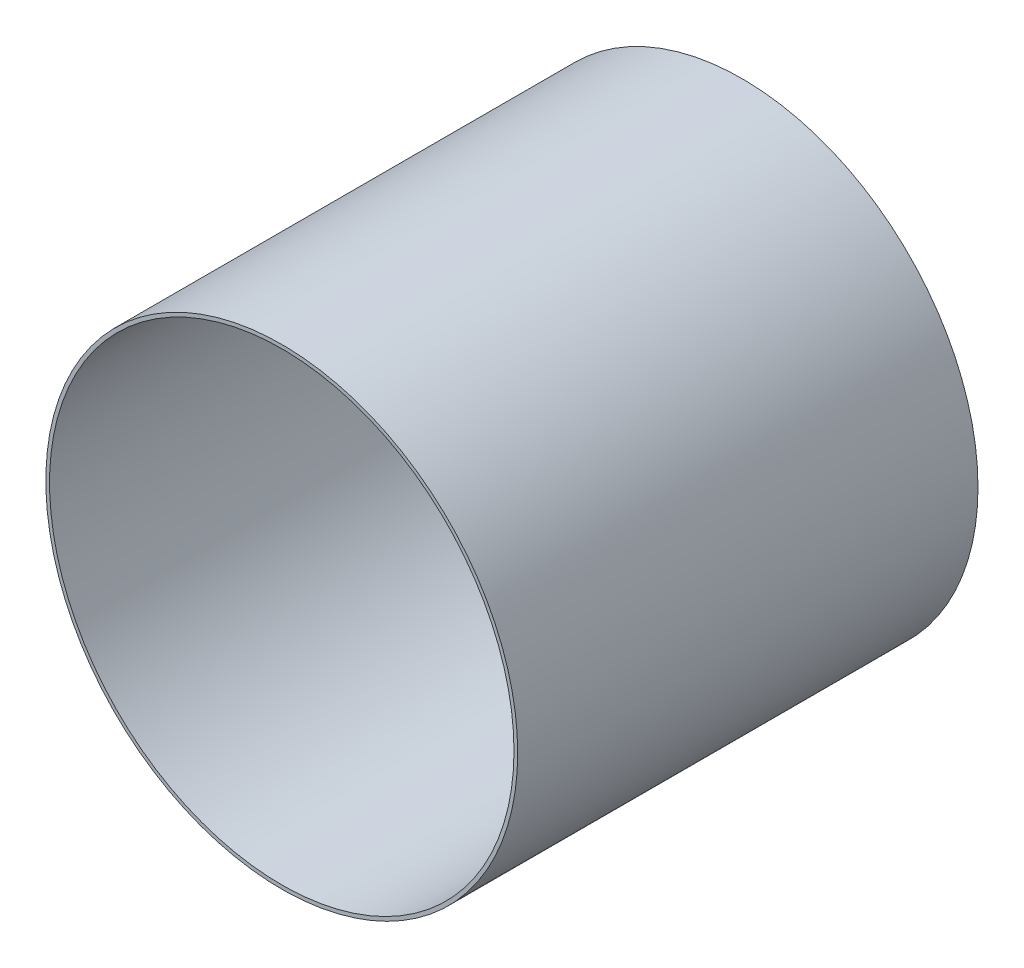
SolidWorks part; units mm, degrees
material "Titanio"
ref_plane "Piano frontale" through (0, 0, 0) normal (0, 0, 1) x (1, 0, 0)
ref_plane "Piano superiore" through (0, 0, 0) normal (0, 1, 0) x (1, 0, 0)
ref_plane "Piano destro" through (0, 0, 0) normal (1, 0, 0) x (0, 0, -1)
sketch "Schizzo1" plane through (0, 0, 0) normal (0, 0, 1) x (1, 0, 0)
  circle A0 centre (0, 0) radius 500
  circle A1 centre (0, 0) radius 492.15
  dimension "D1" = 1000
  dimension "D2" = 7.85
extrude "Estrusione-Estrusione1" add sketch "Schizzo1" along normal blind 975.5
